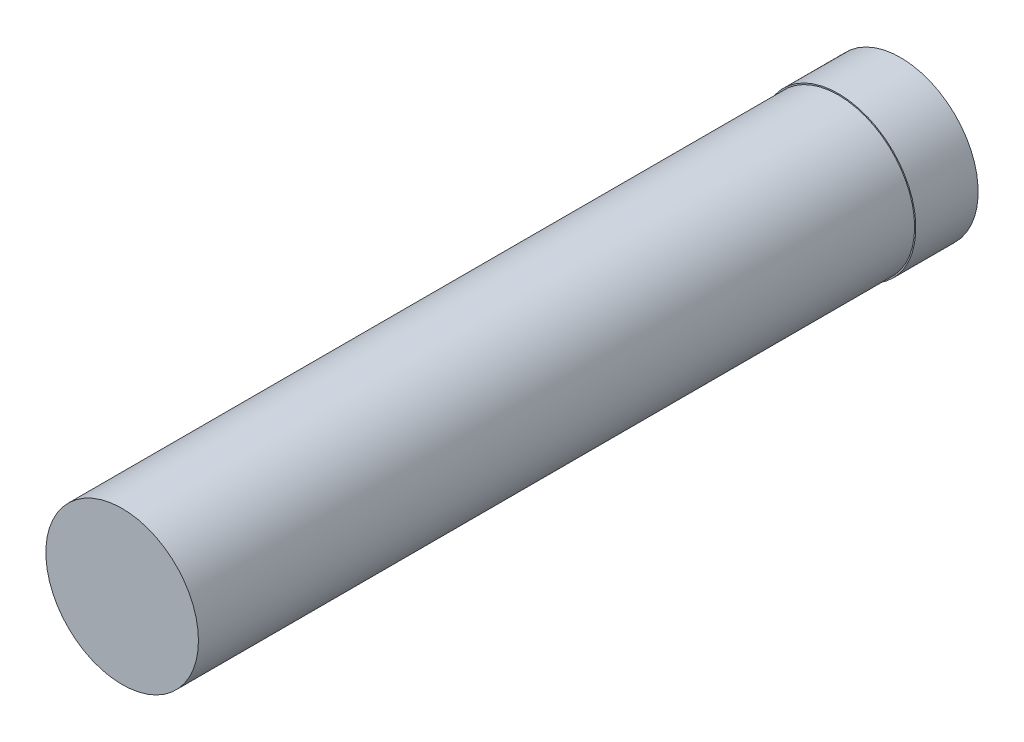
SolidWorks part; units mm, degrees
ref_plane "Front Plane" through (0, 0, 0) normal (0, 0, 1) x (1, 0, 0)
ref_plane "Top Plane" through (0, 0, 0) normal (0, 1, 0) x (1, 0, 0)
ref_plane "Right Plane" through (0, 0, 0) normal (1, 0, 0) x (0, 0, -1)
sketch "Sketch1" plane through (0, 0, 0) normal (0, 0, 1) x (1, 0, 0)
  circle A0 centre (0, 0) radius 2.45
  dimension "D1" = 4.9
extrude "Boss-Extrude1" add sketch "Sketch1" along normal blind 15 and the other way blind 10
sketch "Sketch2" plane through (0, 0, 0) normal (0, 0, 1) x (1, 0, 0)
  circle A0 centre (0, 0) radius 2.5 construction
  dimension "D1" = 5
sketch "Sketch3" plane through (0, 0, -10) normal (0, 0, -1) x (-1, 0, 0)
  circle A0 centre (0, 0) radius 2.49
  dimension "D1" = 4.98
extrude "Boss-Extrude2" add sketch "Sketch3" against normal blind 2
